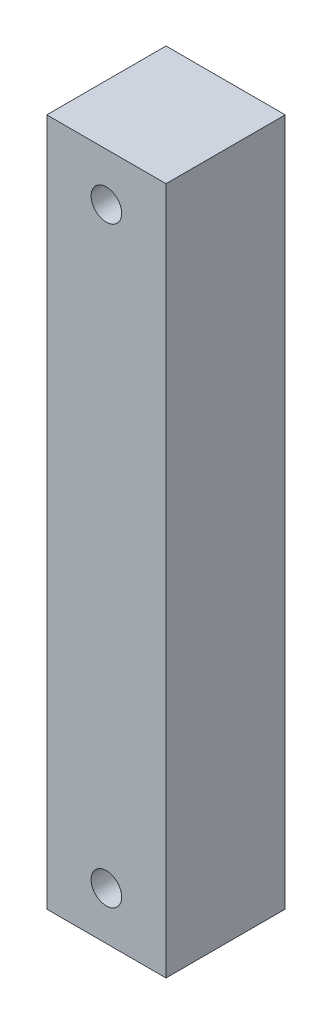
SolidWorks part; units mm, degrees
ref_plane "Front Plane" through (0, 0, 0) normal (0, 0, 1) x (1, 0, 0)
ref_plane "Top Plane" through (0, 0, 0) normal (0, 1, 0) x (1, 0, 0)
ref_plane "Right Plane" through (0, 0, 0) normal (1, 0, 0) x (0, 0, -1)
sketch "Sketch1" plane through (0, 0, 0) normal (0, 1, 0) x (1, 0, 0)
  line L1 (-5.85, 5.85) -> (5.85, 5.85)
  line L2 (-5.85, 5.85) -> (-5.85, -5.85)
  line L3 (-5.85, -5.85) -> (5.85, -5.85)
  line L4 (5.85, 5.85) -> (5.85, -5.85)
  line L5 (-5.85, 5.85) -> (5.85, -5.85) construction
  line L6 (-5.85, -5.85) -> (5.85, 5.85) construction
  point P0 (0, 0)
  dimension "D1" = 11.7
extrude "Boss-Extrude1" add sketch "Sketch1" along normal blind 67.5
sketch "Sketch2" plane through (0, 0, 5.85) normal (0, 0, 1) x (1, 0, 0)
  line L0 (-5.85, 67.5) -> (5.85, 67.5) construction
  circle A0 centre (0, 62.8) radius 1.5
  point P4 (0, 67.5)
  dimension "D1" = 3
  dimension "D2" = 4.7
extrude "Cut-Extrude1" cut sketch "Sketch2" against normal through all
sketch "Sketch3" plane through (0, 0, 5.85) normal (0, 0, 1) x (1, 0, 0)
  line L0 (-5.85, 0) -> (5.85, 0) construction
  circle A0 centre (0, 4.7) radius 1.5
  dimension "D1" = 3
  dimension "D2" = 4.7
extrude "Cut-Extrude2" cut sketch "Sketch3" against normal through all
